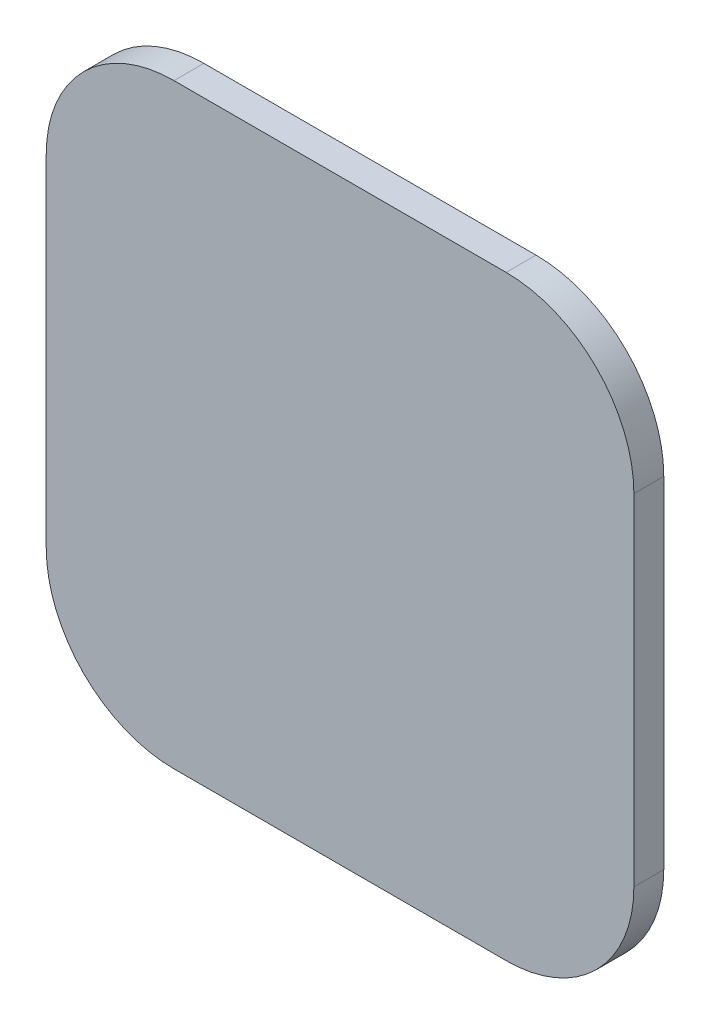
SolidWorks part; units mm, degrees
ref_plane "Front Plane" through (0, 0, 0) normal (0, 0, 1) x (1, 0, 0)
ref_plane "Top Plane" through (0, 0, 0) normal (0, 1, 0) x (1, 0, 0)
ref_plane "Right Plane" through (0, 0, 0) normal (1, 0, 0) x (0, 0, -1)
sketch "Sketch2" plane through (0, 0, 0) normal (0, 0, 1) x (1, 0, 0)
  line L1 (0, 0) -> (23, 0)
  line L2 (0, 0) -> (0, 23.33)
  line L3 (0, 23.33) -> (23, 23.33)
  line L4 (23, 0) -> (23, 23.33)
  line L5 (19.26, 23.33) -> (23.96, 23.33) construction
  dimension "D1" = 23
base flange "Base-Flange1" sketch "Sketch2" thickness 1.17 reverse thickness direction no parameters "D1"=1.65
fillet "Fillet1" radius 5 4 edges at (0, 23.33, -0.585) (0, 0, -0.585) (23, 0, -0.585) (23, 23.33, -0.585)
sketch "Bend-Lines1" [suppressed] plane through (0, 0, 0) normal (0, 1, 0) x (1, 0, 0)
sketch "Bounding-Box1" [suppressed] plane through (0, 0, 0) normal (0, 1, 0) x (1, 0, 0)
sheet metal parameters "Sheet-Metal1" thickness 1.17 parameters "D1"=1.65
flat pattern "Flat-Pattern1" [suppressed]
sketch "Bend-Lines2" plane through (0, 0, 0) normal (0, 1, 0) x (1, 0, 0)
sketch3d "Bounding-Box2" [suppressed]
  line L0 (23, 0, 0) -> (23, 23.33, 0) construction
  line L1 (0, 0, 0) -> (0, 23.33, 0) construction
  line L2 (23, 0, 0) -> (0, 0, 0) construction
  line L3 (23, 23.33, 0) -> (0, 23.33, 0) construction
